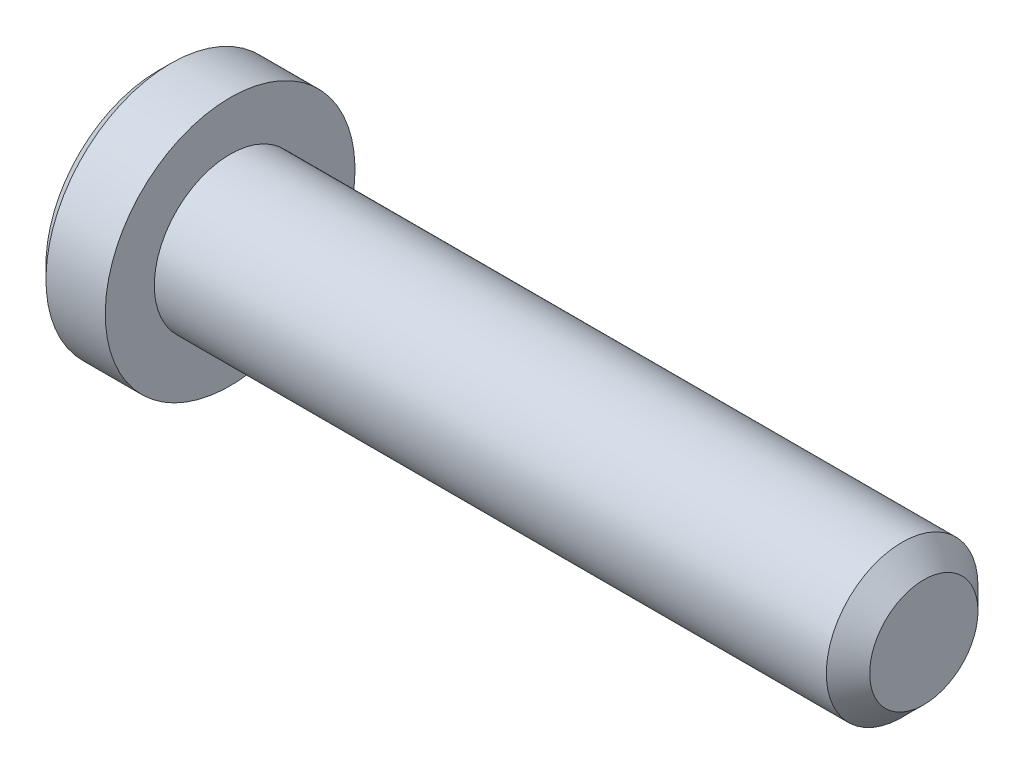
SolidWorks part; units mm, degrees
ref_plane "Front Plane" through (0, 0, 0) normal (0, 0, 1) x (1, 0, 0)
ref_plane "Top Plane" through (0, 0, 0) normal (0, 1, 0) x (1, 0, 0)
ref_plane "Right Plane" through (0, 0, 0) normal (1, 0, 0) x (0, 0, -1)
sketch "Sketch1" plane through (0, 0, 0) normal (0, 0, 1) x (1, 0, 0)
  line L0 (9.525, 0) -> (-9.525, 0) construction
  line L1 (9.525, 2.0828) -> (9.525, -2.0828) construction
  line L2 (-9.525, 3.429) -> (-9.525, -3.429) construction
  line L3 (-9.525, 3.429) -> (-11.1538, 3.429) construction
  line L4 (-11.1538, 3.429) -> (-11.5094, 3.0734) construction
  line L5 (-11.5094, 3.0734) -> (-11.5094, -3.0734) construction
  line L6 (-11.5094, -3.0734) -> (-11.1538, -3.429) construction
  line L7 (-11.1538, -3.429) -> (-9.525, -3.429) construction
  point P7 (-9.9854, 0)
  point P12 (6.35, -2.0828)
  dimension "D1" = 45
  dimension "D2" = 3.175
  dimension "Dec." = 4.1656
  dimension "Length" = 19.05
  dimension "Head Dia" = 6.858
  dimension "Head Height" = 1.9844
  dimension "Hex Depth" = 1.524
  dimension "Chamfer" = 0.3556
ref_plane "Plane1" through (9.525, 0, 0) normal (1, 0, 0) x (0, 0, -1)
ref_plane "Plane2" through (-11.5094, 0, 0) normal (1, 0, 0) x (0, 0, -1)
sketch "Sketch2" plane through (9.525, 0, 0) normal (1, 0, 0) x (0, 0, -1)
  circle A0 centre (0, 0) radius 2.0828
extrude "Boss-Extrude1" add sketch "Sketch2" against normal up to vertex (19.05 mm away) up to point (-9.525, 0, 0)
sketch "Sketch3" plane through (9.525, 0, 0) normal (1, 0, 0) x (0, 0, -1)
  circle A0 centre (0, 0) radius 2.0828 construction
  circle A1 centre (0, 0) radius 2.0828
curve "Helix/Spiral1" pitch 0.7937 height 19.8438 turns 25 parameters "Pitch"=0.7937
chamfer "Chamfer1" distance 0.5953 angle 45 1 edges at (9.525, 0, -2.0828)
sketch "Sketch5" plane through (0, 0, 0) normal (0, 0, 1) x (1, 0, 0)
  line L0 (9.1777, 2.0828) -> (9.8723, 2.0828)
  line L1 (9.8723, 2.0828) -> (9.5746, 1.5672)
  line L2 (9.5746, 1.5672) -> (9.4754, 1.5672)
  line L3 (9.4754, 1.5672) -> (9.1777, 2.0828)
  line L4 (9.525, 1.5672) -> (9.525, 2.0828) construction
  line L5 (9.3266, 1.825) -> (9.7234, 1.825) construction
  dimension "D1" = 60
  dimension "D2" = 0.3969
  dimension "D3" = 0.0992
sweep "Cut-Sweep1" [suppressed] cut profiles "Sketch5" path "Helix/Spiral1"
sketch "Sketch4" plane through (-11.5094, 0, 0) normal (1, 0, 0) x (0, 0, -1)
  line L0 (-3.429, 0.7937) -> (3.429, 0.7937) construction
  line L1 (0, 1.1457) -> (-0.9922, 0.5728)
  line L2 (-0.9922, 0.5728) -> (-0.9922, -0.5728)
  line L3 (-0.9922, -0.5728) -> (0, -1.1457)
  line L4 (0, -1.1457) -> (0.9922, -0.5728)
  line L5 (0.9922, -0.5728) -> (0.9922, 0.5728)
  line L6 (0.9922, 0.5728) -> (0, 1.1457)
  line L7 (0, 0) -> (0, 0.7937) construction
  circle A0 centre (0, 0) radius 0.9922 construction
  dimension "D1" = 6.858
  dimension "Hex Size" = 1.9844
  dimension "D2" = 0.7937
sketch "Sketch6" plane through (0, 0, 0) normal (0, 0, 1) x (1, 0, 0)
  line L0 (-11.1538, 3.429) -> (-11.5094, 3.0734) construction
  line L1 (-9.525, 3.429) -> (-11.1538, 3.429) construction
  line L2 (-9.525, 3.429) -> (-9.525, -3.429) construction
  line L3 (-11.5094, 3.0734) -> (-11.5094, -3.0734) construction
  line L4 (-11.1538, 3.429) -> (-11.5094, 3.0734)
  line L5 (-9.525, 3.429) -> (-11.1538, 3.429)
  line L6 (-9.525, 3.429) -> (-9.525, 0)
  line L7 (-11.5094, 3.0734) -> (-11.5094, 0)
  line L8 (-9.525, 0) -> (-11.5094, 0) construction
  line L9 (-9.525, 0) -> (-11.5094, 0)
revolve "Revolve1" add sketch "Sketch6" angle 360 about L8
extrude "Cut-Extrude1" cut sketch "Sketch4" along normal up to vertex (1.524 mm away) up to point (-9.9854, 0, 0)
sketch "Sketch8" plane through (-11.5094, 0, 0) normal (-1, 0, 0) x (0, 0, 1)
  circle A1 centre (0, 0) radius 1.1457
extrude "Cut-Extrude2" cut sketch "Sketch8" against normal through all draft 45
equation "\"D3@Helix/Spiral1\" = \"Length@Sketch1\"+\"Pitch@Helix/Spiral1\""
equation "\"D3@Sketch5\" = \"Pitch@Helix/Spiral1\"*.125"
equation "\"D2@Sketch5\" = \"Pitch@Helix/Spiral1\"*.50"
equation "\"D1@Chamfer1\" = \"Pitch@Helix/Spiral1\"*.75"
equation "\"D2@Sketch1\" = \"Pitch@Helix/Spiral1\"*4"
equation "\"D1@Sketch4\" = \"Head Dia@Sketch1\""
